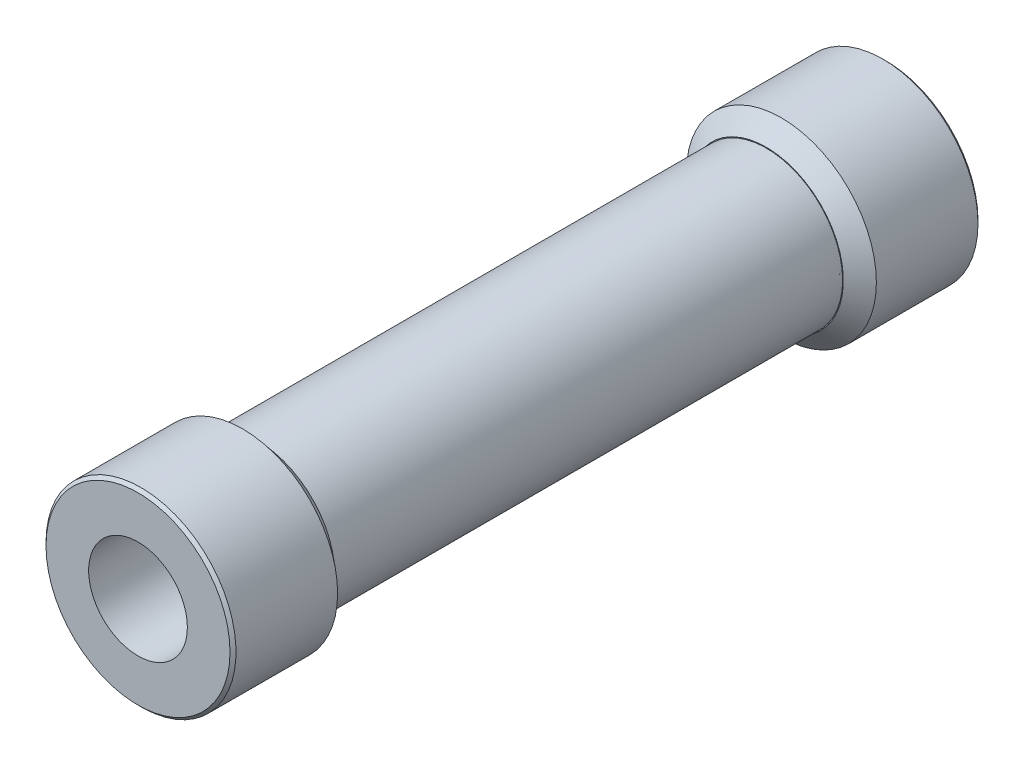
SolidWorks part; units mm, degrees
ref_plane "Ön Düzlem" through (0, 0, 0) normal (0, 0, 1) x (1, 0, 0)
ref_plane "Üst Düzlem" through (0, 0, 0) normal (0, 1, 0) x (1, 0, 0)
ref_plane "Sağ Düzlem" through (0, 0, 0) normal (1, 0, 0) x (0, 0, -1)
sketch "Çizim1" plane through (0, 0, 0) normal (1, 0, 0) x (0, 0, -1)
  line L0 (-15.5449, 0) -> (9.4551, 0) construction
  line L1 (-8.5, 0) -> (8.5, 0)
  line L2 (8.5, 0) -> (8.5, -2.55)
  line L7 (8.5, 0) -> (13.7667, 0)
  line L8 (8.5, -2.55) -> (-8.5, -2.55)
  line L9 (-8.5, -2.55) -> (-8.5, 0)
  point P5 (0, 0)
  dimension "D1" = 25
  dimension "D2" = 17
  dimension "D3" = 2.55
revolve "Döndür3" add sketch "Çizim1" angle 360 about L0 region at (0, -1.275, 0)
sketch "Çizim4" plane through (0, 0, -8.5) normal (0, 0, -1) x (-1, 0, 0)
  circle A0 centre (0, 0) radius 2.575
  dimension "D1" = 5.15
extrude "Yükseklik-Ekstrüzyon1" add sketch "Çizim4" along normal blind 0.6
sketch "Çizim5" plane through (0, 0, -9.1) normal (0, 0, -1) x (-1, 0, 0)
  circle A0 centre (0, 0) radius 3.175
  dimension "D1" = 6.35
extrude "Yükseklik-Ekstrüzyon2" add sketch "Çizim5" along normal blind 3.4
draft "Draft2" type of draft neutral plane draft angle 50 faces to draft 1 face at (-2.575, 0, -9.1) neutral plane through (0, 0, -8.5) neutral plane normal (0, 0, 1) parameters "D1"=50
sketch "Çizim7" plane through (0, 0, 8.5) normal (0, 0, 1) x (1, 0, 0)
  circle A0 centre (0, 0) radius 2.575
  dimension "D1" = 5.15
extrude "Yükseklik-Ekstrüzyon4" add sketch "Çizim7" along normal blind 0.6
sketch "Çizim8" plane through (0, 0, 9.1) normal (0, 0, 1) x (1, 0, 0)
  circle A0 centre (0, 0) radius 3.175
  dimension "D1" = 6.35
extrude "Yükseklik-Ekstrüzyon5" add sketch "Çizim8" along normal blind 3.4
draft "Draft3" type of draft neutral plane draft angle 50 faces to draft 1 face at (2.575, 0, 9.1) neutral plane through (0, 0, 8.5) neutral plane normal (0, 0, -1) parameters "D1"=50
sketch "Çizim9" plane through (0, 0, 12.5) normal (0, 0, 1) x (1, 0, 0)
  circle A0 centre (0, 0) radius 1.65
  dimension "D1" = 3.3
extrude "Kes-Ekstrüzyon1" cut sketch "Çizim9" against normal blind 100
chamfer "Pah1" distance 0.1 angle 45 2 edges at (3.175, 0, 12.5) (-3.175, 0, -12.5)
